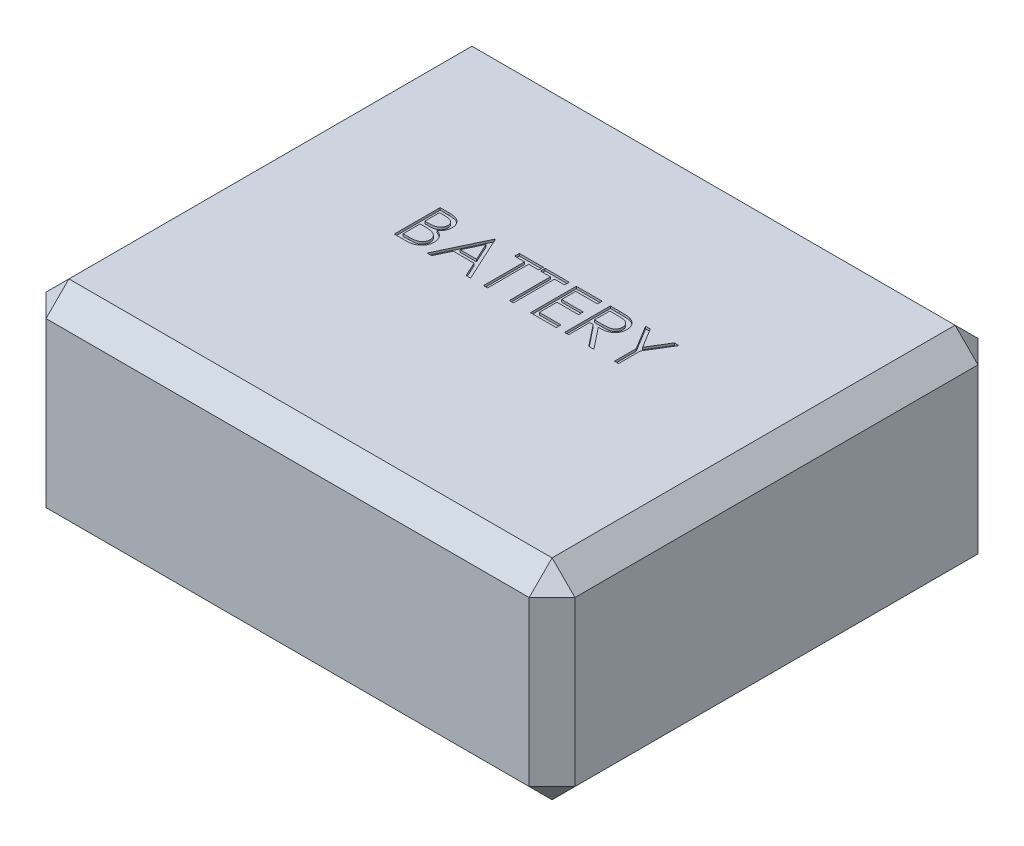
SolidWorks part; units mm, degrees
ref_plane "Front Plane" through (0, 0, 0) normal (0, 0, 1) x (1, 0, 0)
ref_plane "Top Plane" through (0, 0, 0) normal (0, 1, 0) x (1, 0, 0)
ref_plane "Right Plane" through (0, 0, 0) normal (1, 0, 0) x (0, 0, -1)
sketch "Sketch1" plane through (0, 0, 0) normal (0, 1, 0) x (1, 0, 0)
  line L1 (0, 0) -> (231, 0)
  line L2 (0, 0) -> (0, 196)
  line L3 (0, 196) -> (231, 196)
  line L4 (231, 0) -> (231, 196)
  dimension "D1" = 196
  dimension "D2" = 231
extrude "Boss-Extrude1" add sketch "Sketch1" along normal blind 91.5
sketch "Sketch2" plane through (0, 91.5, 0) normal (0, 1, 0) x (1, 0, 0)
  line L0 (0, 98) -> (231, 98) construction
  line L1 (0, 196) -> (0, 0) construction
  line L2 (231, 0) -> (231, 196) construction
  text T0 "BATTERY" font "Century Gothic" height 20
extrude "Cut-Extrude1" cut sketch "Sketch2" against normal blind 1
chamfer "Chamfer1" distance 10 angle 45 12 edges at (0, 91.5, -98) (0, 0, -98) (115.5, 91.5, -196) (0, 45.75, -196) (115.5, 0, -196) (231, 91.5, -98) (231, 45.75, -196) (231, 0, -98) (0, 45.75, 0) (115.5, 91.5, 0) (231, 45.75, 0) (115.5, 0, 0)
